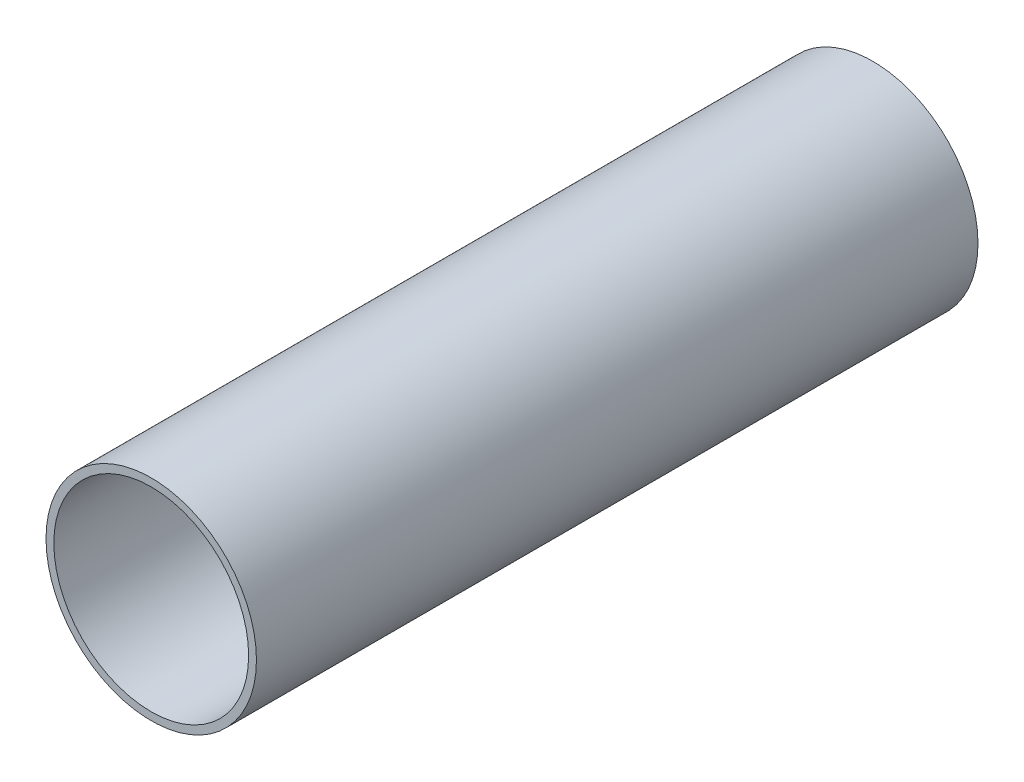
SolidWorks part; units mm, degrees
material "Hexcel AS4C (3000 Filaments)"
ref_plane "Front Plane" through (0, 0, 0) normal (0, 0, 1) x (1, 0, 0)
ref_plane "Top Plane" through (0, 0, 0) normal (0, 1, 0) x (1, 0, 0)
ref_plane "Right Plane" through (0, 0, 0) normal (1, 0, 0) x (0, 0, -1)
sketch "Sketch1" plane through (0, 0, 0) normal (0, 0, 1) x (1, 0, 0)
  circle A0 centre (0, 0) radius 22.225
  circle A1 centre (0, 0) radius 20.574
  dimension "D1" = 44.45
  dimension "D2" = 41.148
extrude "Boss-Extrude1" add sketch "Sketch1" along normal blind 152.4
